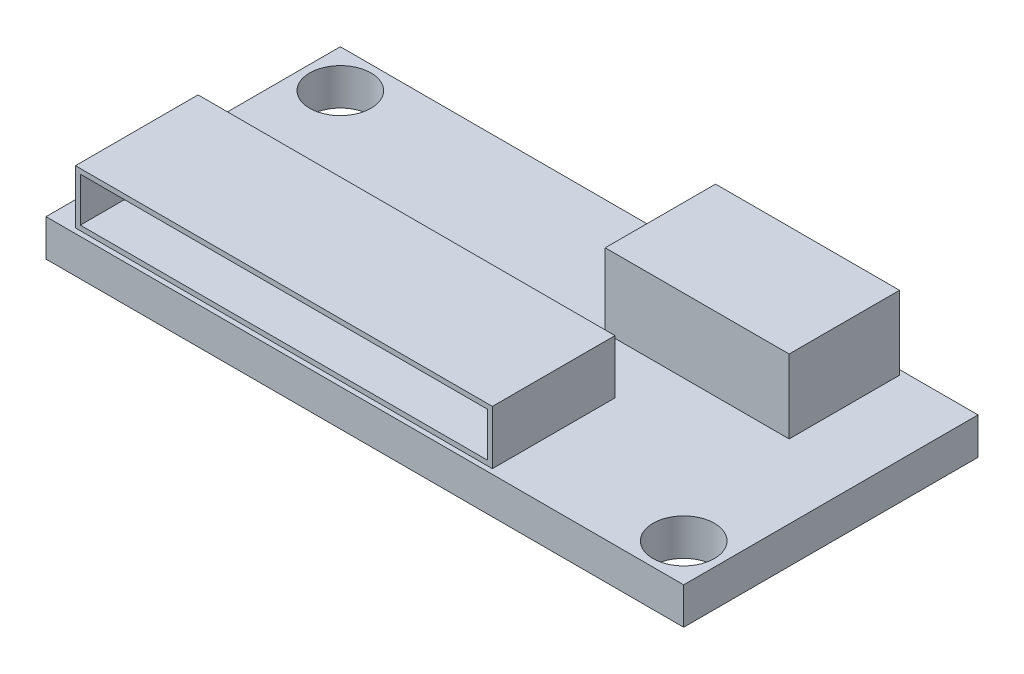
SolidWorks part; units mm, degrees
ref_plane "Front Plane" through (0, 0, 0) normal (0, 0, 1) x (1, 0, 0)
ref_plane "Top Plane" through (0, 0, 0) normal (0, 1, 0) x (1, 0, 0)
ref_plane "Right Plane" through (0, 0, 0) normal (1, 0, 0) x (0, 0, -1)
sketch "Sketch1" plane through (0, 0, 0) normal (0, 1, 0) x (1, 0, 0)
  line L1 (0, 0) -> (26, 0)
  line L2 (0, 0) -> (0, 12)
  line L3 (0, 12) -> (26, 12)
  line L4 (26, 0) -> (26, 12)
  circle A0 centre (1.55, 10.45) radius 1.25
  circle A1 centre (24.45, 1.55) radius 1.25
  dimension "D3" = 2.5
  dimension "D1" = 26
  dimension "D2" = 12
  dimension "D4" = 1.55
  dimension "D5" = 1.55
  dimension "D6" = 1.55
  dimension "D7" = 1.55
extrude "Boss-Extrude1" add sketch "Sketch1" along normal blind 1.5
sketch "Sketch2" plane through (0, 1.5, 0) normal (0, 1, 0) x (1, 0, 0)
  line L0 (0, 0) -> (26, 0) construction
  line L1 (1, 5.2) -> (18, 5.2)
  line L2 (1, 5.2) -> (1, 0.2)
  line L3 (1, 0.2) -> (18, 0.2)
  line L4 (18, 5.2) -> (18, 0.2)
  line L5 (0, 12) -> (0, 0) construction
  line L6 (26, 0) -> (26, 12) construction
  line L7 (26, 12) -> (0, 12) construction
  line L8 (15.5, 11.8) -> (23, 11.8)
  line L9 (15.5, 11.8) -> (15.5, 7.3)
  line L10 (15.5, 7.3) -> (23, 7.3)
  line L11 (23, 11.8) -> (23, 7.3)
  dimension "D1" = 17
  dimension "D2" = 5
  dimension "D3" = 0.2
  dimension "D4" = 1
  dimension "D5" = 8
  dimension "D6" = 7.5
  dimension "D7" = 4.5
  dimension "D8" = 3
  dimension "D9" = 0.2
extrude "Boss-Extrude2" add sketch "Sketch2" along normal blind 2.2 contours L4 L1 L2 L3 region at (9.5, 1.5, -2.7)
extrude "Boss-Extrude3" add sketch "Sketch2<3>" along normal blind 3 contours L11 L8 L9 L10 region at (19.25, 1.5, -9.55)
sketch "Sketch2<3>" plane through (0, 1.5, 0) normal (0, 1, 0) x (1, 0, 0) same geometry as "Sketch2"
sketch "Sketch3" plane through (0, 0, -11.8) normal (0, 0, -1) x (-1, 0, 0)
  line L8 (-22.8, 1.7) -> (-15.7, 1.7)
  line L9 (-15.7, 1.7) -> (-15.7, 4.3)
  line L10 (-15.7, 4.3) -> (-22.8, 4.3)
  line L11 (-22.8, 4.3) -> (-22.8, 1.7)
  line L12 (-22.8, 1.7) -> (-15.7, 1.7)
  line L13 (-15.7, 1.7) -> (-15.7, 4.3)
  line L14 (-15.7, 4.3) -> (-22.8, 4.3)
  line L15 (-22.8, 4.3) -> (-22.8, 1.7)
  dimension "D1" = 0.2
extrude "Cut-Extrude1" cut sketch "Sketch3" against normal offset from surface (4.3 mm away) 0.2 up to face at (19.25, 3, -7.3)
sketch "Sketch4" plane through (0, 0, -0.2) normal (0, 0, 1) x (1, 0, 0)
  line L9 (1.2, 1.7) -> (17.8, 1.7)
  line L10 (17.8, 1.7) -> (17.8, 3.5)
  line L11 (17.8, 3.5) -> (1.2, 3.5)
  line L12 (1.2, 3.5) -> (1.2, 1.7)
  line L13 (1.2, 1.7) -> (17.8, 1.7)
  line L14 (17.8, 1.7) -> (17.8, 3.5)
  line L15 (17.8, 3.5) -> (1.2, 3.5)
  line L16 (1.2, 3.5) -> (1.2, 1.7)
  dimension "D1" = 0.2
extrude "Cut-Extrude2" cut sketch "Sketch4" against normal offset from surface (4.8 mm away) 0.2 up to face at (9.5, 2.6, -5.2)
sketch "Sketch5" plane through (0, 0, 0) normal (0, -1, 0) x (1, 0, 0)
  line L0 (0, -12) -> (0, 0) construction
  line L1 (6, -6.6) -> (12.5, -6.6)
  line L2 (6, -6.6) -> (6, -10.6)
  line L3 (6, -10.6) -> (12.5, -10.6)
  line L4 (12.5, -6.6) -> (12.5, -10.6)
  line L5 (26, -12) -> (0, -12) construction
  dimension "D1" = 6.5
  dimension "D2" = 4
  dimension "D3" = 6
  dimension "D4" = 1.4
extrude "Boss-Extrude4" add sketch "Sketch5" along normal blind 0.8
equation "\"D4@Sketch1\"=0.3+\"D3@Sketch1\"/2"
equation "\"D5@Sketch1\"=\"D4@Sketch1\""
equation "\"D6@Sketch1\"=\"D4@Sketch1\""
equation "\"D7@Sketch1\"=\"D4@Sketch1\""
